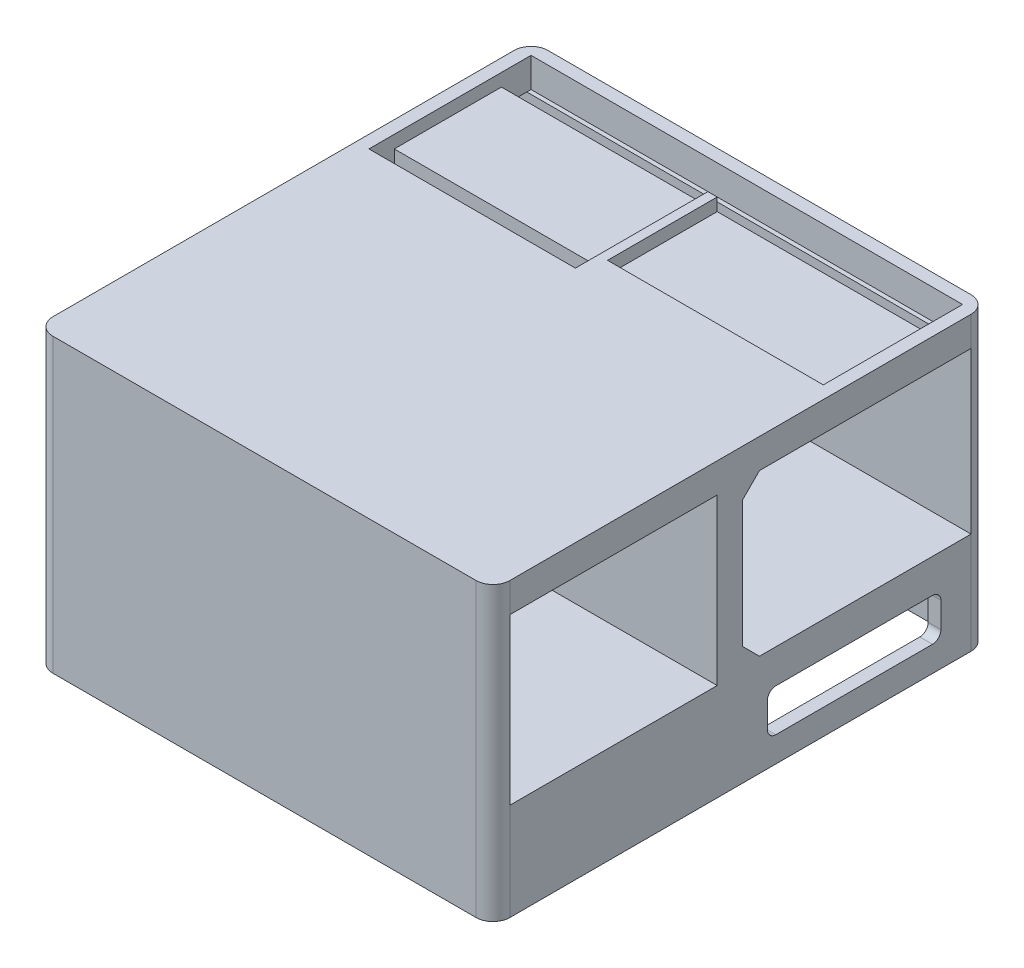
SolidWorks part; units mm, degrees
note: The reader was unsure of these and kept them because the rebuilt part matched: shared geometry of "Sketch3<3>", "Sketch3<5>".
ref_plane "前视基准面" through (0, 0, 0) normal (0, 0, 1) x (1, 0, 0)
ref_plane "上视基准面" through (0, 0, 0) normal (0, 1, 0) x (1, 0, 0)
ref_plane "右视基准面" through (0, 0, 0) normal (1, 0, 0) x (0, 0, -1)
sketch "Sketch3" plane through (0, 0, 0) normal (0, 1, 0) x (1, 0, 0)
  line L0 (-27, 15) -> (-27, 16.5)
  line L1 (-25.5, 12) -> (25.5, 12)
  line L2 (-25.5, 12) -> (-25.5, -10)
  line L3 (-23.5, -12) -> (23.5, -12)
  line L4 (25.5, 12) -> (25.5, -10)
  line L5 (-25.5, 12) -> (25.5, -12) construction
  line L6 (-25.5, -12) -> (25.5, 12) construction
  line L7 (-25.5, 12) -> (25.5, 12)
  line L8 (-25.5, 12) -> (-25.5, 13)
  line L9 (-23.5, 15.5) -> (23.5, 15.5)
  line L10 (25.5, 12) -> (25.5, 13)
  line L11 (-23.5, 15.5) -> (23.5, 15.5)
  line L12 (-27, 13) -> (-27, -11.5)
  line L13 (-25, -13.5) -> (25, -13.5)
  line L14 (27, 13) -> (27, -11.5)
  line L15 (-25, 17) -> (25, 17)
  line L16 (27, 16.5) -> (27, 15)
  line L17 (27, 15) -> (27, 13)
  line L18 (23.5, 15.5) -> (0, 15.5)
  line L19 (25.5, 13) -> (25.5, -0.5)
  line L22 (-25.5, 12) -> (-1.1, 12)
  line L23 (-25.5, 12) -> (-25.5, -3.66)
  line L24 (-25.5, -3.66) -> (-1.1, -3.66)
  line L25 (-1.1, 12) -> (-1.1, -3.66)
  line L30 (0, 12) -> (25.5, 12)
  line L31 (0, 12) -> (0, -0.96)
  line L32 (0, -0.96) -> (25.5, -0.96)
  line L33 (25.5, 12) -> (25.5, -0.96)
  line L34 (-27, 15) -> (-27, 13)
  line L35 (-25.5, -0.66) -> (-1.1, -0.66)
  line L36 (-23.5, 15.5) -> (-25.5, 15.5)
  line L37 (-25.5, 15.5) -> (-25.5, 13)
  line L38 (25.5, 13) -> (25.5, 15.5)
  line L39 (25.5, 15.5) -> (23.5, 15.5)
  line L40 (-27, -11.5) -> (-27, -39.5)
  line L41 (-25, -41.5) -> (25, -41.5)
  line L42 (27, -11.5) -> (27, -39.5)
  line L43 (27, -39.5) -> (25.5, -39.5)
  line L45 (-25, -13.5) -> (25, -13.5)
  line L46 (-25, -13.5) -> (-25, -38)
  line L47 (-25, -38) -> (25, -38)
  line L48 (25, -13.5) -> (25, -38)
  arc A2 (-27, -11.5) -> (-25, -13.5) centre (-25, -11.5) ccw
  arc A3 (27, -11.5) -> (25, -13.5) centre (25, -11.5) cw
  arc A6 (-25.5, -10) -> (-23.5, -12) centre (-23.5, -10) ccw
  arc A7 (23.5, -12) -> (25.5, -10) centre (23.5, -10) ccw
  arc A8 (-27, 15) -> (-25, 17) centre (-25, 15) cw
  arc A9 (27, 15) -> (25, 17) centre (25, 15) ccw
  arc A10 (25, -41.5) -> (27, -39.5) centre (25, -39.5) ccw
  arc A11 (-25, -41.5) -> (-27, -39.5) centre (-25, -39.5) cw
  point P0 (0, 0)
  point P34 (-25.5, 15.5)
  dimension "D12" = 2
  dimension "D16" = 2
  dimension "D1" = 51
  dimension "D2" = 24
  dimension "D3" = 3.5
  dimension "D4" = 1.5
  dimension "D5" = 1.5
  dimension "D6" = 1.5
  dimension "D7" = 1.5
  dimension "D8" = 12.96
  dimension "D9" = 25.5
  dimension "D10" = 15.66
  dimension "D11" = 24.4
  dimension "D13" = 3
  dimension "D14" = 28
  dimension "D15" = 24.5
extrude "Boss-Extrude4" add sketch "Sketch3" against normal blind 21 contours L16 L15 L0 L11 L9 | L14 L11 L10 L4 L3 L2 L8 L12 L13 | L25 L1 L2 L24 | L31 L32 L4 L1 | L32 L31 L7 L25 L24 L2 L3 L4 | L35 L23 L24 L25 | A11 L41 A10 L42 A3 L48 L47 L46 A2 L40 | L48 L13 L46 L47
extrude "Boss-Extrude5" add sketch "Sketch3<3>" along normal blind 3.5
sketch "Sketch3<3>" plane through (0, 0, 0) normal (0, 1, 0) x (1, 0, 0) same geometry as "Sketch3"
sketch "Sketch4" plane through (-27, 0, 0) normal (-1, 0, 0) x (0, 0, 1)
  line L5 (-15, 0) -> (12, 0)
  line L6 (-15, 0) -> (-15, -19)
  line L7 (-15, -19) -> (12, -19)
  line L8 (12, 0) -> (12, -19)
  line L9 (-15, 0) -> (12, -19) construction
  line L10 (-15, -19) -> (12, 0) construction
  point P6 (-1.5, -9.5)
extrude "Cut-Extrude4" cut sketch "Sketch4" against normal through all
extrude "Boss-Extrude6" add sketch "Sketch3<5>" along normal blind 2 contours L2 L35 L25 L1 | L31 L32 L4 L1
sketch "Sketch3<5>" plane through (0, 0, 0) normal (0, 1, 0) x (1, 0, 0) same geometry as "Sketch3"
sketch "Sketch5" plane through (0, -21, 0) normal (0, -1, 0) x (1, 0, 0)
  line L1 (-25.5, 13.5) -> (25.5, 13.5)
  line L3 (-25.5, -15.5) -> (25.5, -15.5)
  line L5 (25.5, -15.5) -> (25.5, 13.5)
  line L6 (-25.5, -15.5) -> (-25.5, 13.5)
  dimension "D1" = 29
extrude "Boss-Extrude7" add sketch "Sketch5" along normal blind 10
sketch "Sketch6" plane through (-27, 0, 0) normal (-1, 0, 0) x (0, 0, 1)
  line L0 (39.5, -31) -> (-15, -31) construction
  line L1 (-10.4388, -23) -> (8.0612, -23)
  line L2 (-11.4388, -24) -> (-11.4388, -27)
  line L3 (-10.4388, -28) -> (8.0612, -28)
  line L4 (9.0612, -24) -> (9.0612, -27)
  line L5 (-11.4388, -23) -> (9.0612, -28) construction
  line L6 (-11.4388, -28) -> (9.0612, -23) construction
  arc A0 (-11.4388, -24) -> (-10.4388, -23) centre (-10.4388, -24) cw
  arc A1 (8.0612, -23) -> (9.0612, -24) centre (8.0612, -24) cw
  arc A2 (9.0612, -27) -> (8.0612, -28) centre (8.0612, -27) cw
  arc A3 (-10.4388, -28) -> (-11.4388, -27) centre (-10.4388, -27) cw
  point P0 (-1.1888, -25.5)
  dimension "D4" = 1
  dimension "D1" = 3
  dimension "D2" = 20.5
  dimension "D3" = 5
extrude "Cut-Extrude5" cut sketch "Sketch6" against normal through all
sketch "Sketch8" plane through (27, 0, 0) normal (1, 0, 0) x (0, 0, -1)
  line L0 (29.7, 0) -> (-29.7, 0) construction
  line L1 (-15, 0) -> (-39.5, 0)
  line L2 (-15, 0) -> (-15, -19.5)
  line L3 (-15, -19.5) -> (-39.5, -19.5)
  line L4 (-39.5, 0) -> (-39.5, -19.5)
  line L5 (-39.5, -31) -> (-39.5, 3.5) construction
  dimension "D1" = 0
  dimension "D2" = 24.5
  dimension "D3" = 19.5
extrude "Cut-Extrude6" cut sketch "Sketch8" against normal up to next
chamfer "Chamfer1" distance 2 angle 45 10 edges at (25.5, -26, 13.5) (-25.5, -26, 13.5) (-25.5, -26, -15.5) (25.5, -26, -15.5) (-25.5, -21, -1) (0, -21, 13.5) (25.5, -21, -1) (0, -21, -15.5) (0, 0, 12) (0, -19, 12)
